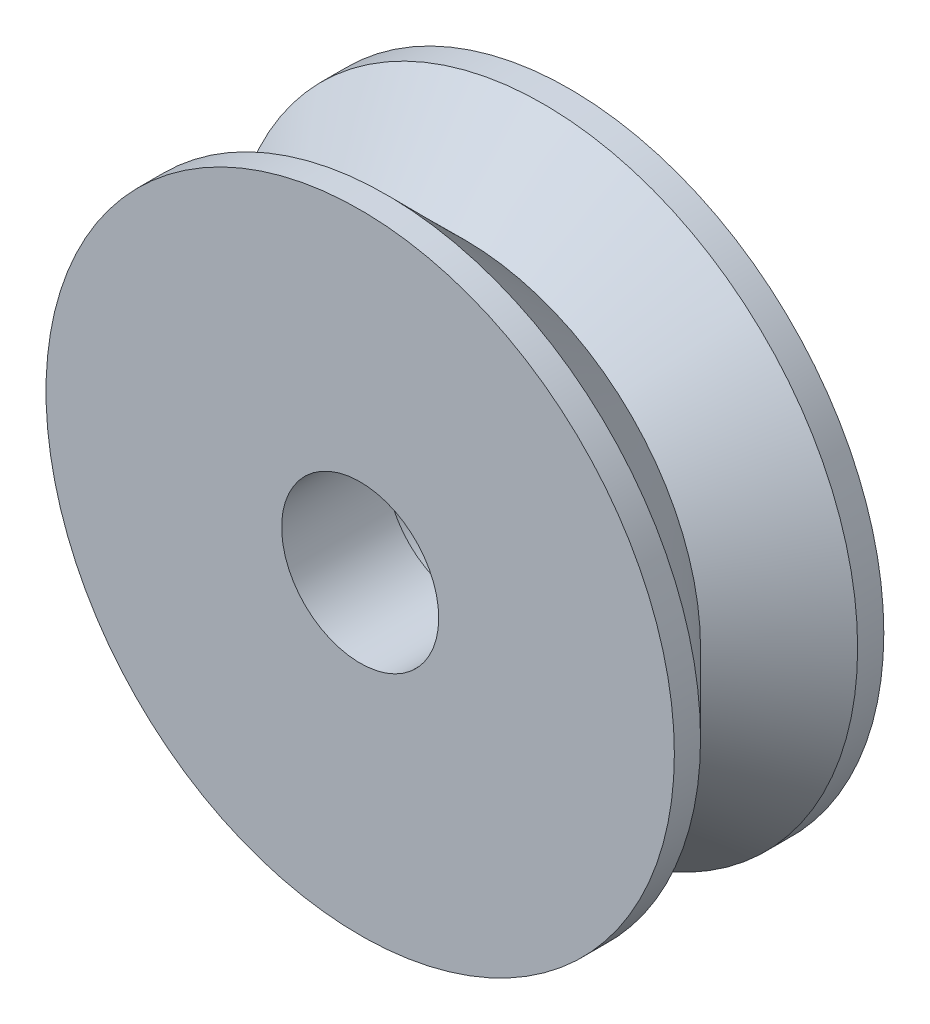
SolidWorks part; units mm, degrees
ref_plane "Front Plane" through (0, 0, 0) normal (0, 0, 1) x (1, 0, 0)
ref_plane "Top Plane" through (0, 0, 0) normal (0, 1, 0) x (1, 0, 0)
ref_plane "Right Plane" through (0, 0, 0) normal (1, 0, 0) x (0, 0, -1)
sketch "Sketch1" plane through (0, 0, 0) normal (0, 0, 1) x (1, 0, 0)
  circle A0 centre (0, 0) radius 6
  circle A1 centre (0, 0) radius 1.7
  dimension "D1" = 3.4
  dimension "D2" = 12
extrude "Boss-Extrude1" add sketch "Sketch1" along normal blind 2
chamfer "Chamfer1" distance 1.5 angle 45 1 edges at (6, 0, 2)
sketch "Sketch2" plane through (0, 0, 2) normal (0, 0, 1) x (1, 0, 0)
  circle A0 centre (0, 0) radius 6
  circle A1 centre (0, 0) radius 1.5
  circle A2 centre (0, 0) radius 4.5 construction
  dimension "D1" = 3
  dimension "D2" = 12
extrude "Boss-Extrude2" add sketch "Sketch2" along normal blind 2
chamfer "Chamfer2" distance 1.5 angle 45 1 edges at (6, 0, 2)
equation "\"D1@Sketch1\"= 3 + \"tol1@parametersSketch@prostheticParameters.SLDPRT\" * 2"
